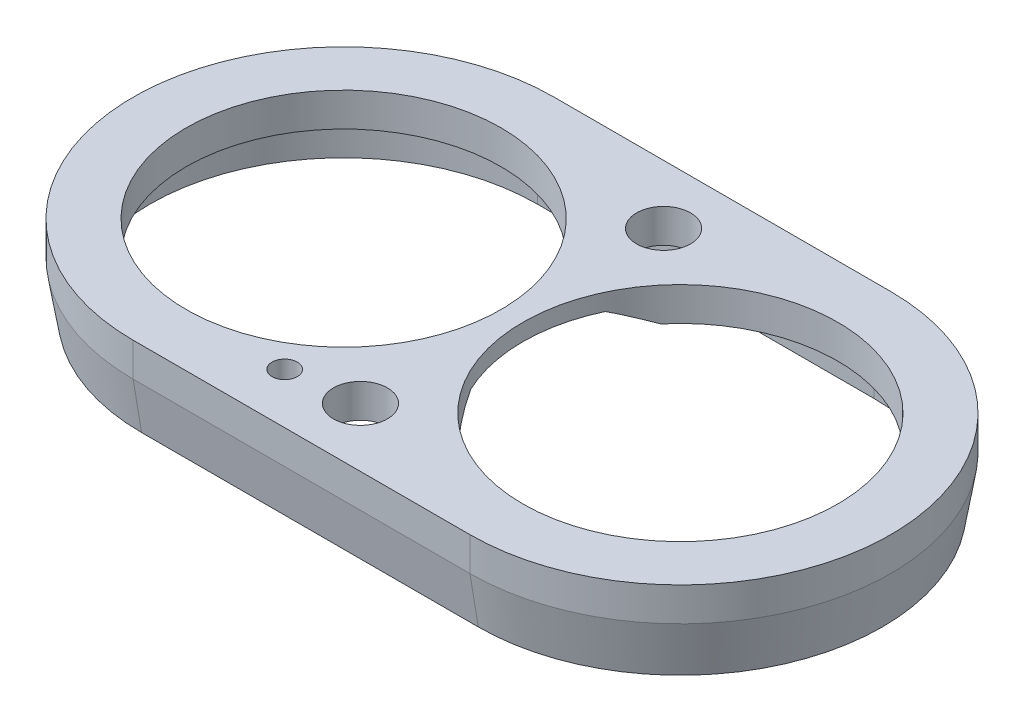
SolidWorks part; units mm, degrees
ref_plane "Front Plane" through (0, 0, 0) normal (0, 0, 1) x (1, 0, 0)
ref_plane "Top Plane" through (0, 0, 0) normal (0, 1, 0) x (1, 0, 0)
ref_plane "Right Plane" through (0, 0, 0) normal (1, 0, 0) x (0, 0, -1)
sketch "Sketch1" plane through (0, 0, 0) normal (0, 1, 0) x (1, 0, 0)
  line L2 (10, -12.5) -> (-10, -12.5)
  line L3 (0, -12.5) -> (0, 12.5)
  line L4 (-0.65, 0) -> (0.65, 0)
  line L6 (31.3696, 0) -> (-34.9839, 0) construction
  line L7 (0, -23.2241) -> (0, 19.3171) construction
  line L8 (10, 12.5) -> (-10, 12.5)
  arc A1 (10, 12.5) -> (10, -12.5) centre (10, 0) cw
  arc A2 (-10, 12.5) -> (-10, -12.5) centre (-10, 0) ccw
  point P22 (0, 0)
  dimension "D2" = 12.5
  dimension "D1" = 10
extrude "Boss-Extrude1" add sketch "Sketch1" along normal blind 2 contours A1 L8 L3 L2 | L8 A2 L2 L3 region at (10.1051, 0, 0) region at (-10.1051, 0, 0)
sketch "Sketch2" plane through (0, 2, 0) normal (0, 1, 0) x (1, 0, 0)
  line L1 (0, 16.1172) -> (0, -16.1351) construction
  circle A0 centre (10, 0) radius 9.35
  circle A1 centre (-10, 0) radius 9.35
  dimension "D2" = 18.7
  dimension "D1" = 10
extrude "Cut-Extrude1" cut sketch "Sketch2" against normal through all
sketch "Sketch3" plane through (0, 0, 0) normal (0, -1, 0) x (1, 0, 0)
  line L4 (-10, -11.5) -> (10, -11.5)
  line L5 (10, 11.5) -> (-10, 11.5)
  line L6 (-10, -11.5) -> (10, -11.5)
  line L7 (10, 11.5) -> (-10, 11.5)
  line L10 (-10, -12.5) -> (10, -12.5)
  line L11 (10, 12.5) -> (-10, 12.5)
  line L12 (-10, -12.5) -> (10, -12.5)
  line L13 (10, 12.5) -> (-10, 12.5)
  arc A4 (10, -11.5) -> (10, 11.5) centre (10, 0) ccw
  arc A5 (-10, 11.5) -> (-10, -11.5) centre (-10, 0) ccw
  arc A6 (10, -11.5) -> (10, 11.5) centre (10, 0) ccw
  arc A7 (-10, 11.5) -> (-10, -11.5) centre (-10, 0) ccw
  arc A10 (10, -12.5) -> (10, 12.5) centre (10, 0) ccw
  arc A11 (-10, 12.5) -> (-10, -12.5) centre (-10, 0) ccw
  arc A12 (10, -12.5) -> (10, 12.5) centre (10, 0) ccw
  arc A13 (-10, 12.5) -> (-10, -12.5) centre (-10, 0) ccw
  dimension "D1" = 1
  dimension "D2" = 0
extrude "Boss-Extrude3" add sketch "Sketch3" along normal blind 3
chamfer "Chamfer1" distance 3 distance2 0.5 4 edges at (22.5, -3, 0) (0, -3, -12.5) (0, -3, 12.5) (-22.5, -3, 0) first distance on face at (16.25, -0.5, 0) first distance on face at (0, -0.5, -12.5) first distance on face at (0, -0.5, 12.5) first distance on face at (-16.25, -0.5, 0)
sketch "Sketch5" plane through (0, 0, 0) normal (0, -1, 0) x (1, 0, 0)
  line L1 (-7.5, -6) -> (7.5, -6)
  line L2 (-7.5, -6) -> (-7.5, 6)
  line L3 (-7.5, 6) -> (7.5, 6)
  line L4 (7.5, -6) -> (7.5, 6)
  line L5 (-7.5, -6) -> (7.5, 6) construction
  line L6 (-7.5, 6) -> (7.5, -6) construction
  point P0 (0, 0)
  dimension "D1" = 15
  dimension "D2" = 12
extrude "Cut-Extrude3" cut sketch "Sketch5" against normal blind 1
chamfer "Chamfer2" distance 1 distance2 2 2 edges at (0, 1, -6) (0, 1, 6) first distance on face at (0, 0.5, -6) first distance on face at (0, 0.5, 6)
sketch "Sketch7" plane through (0, 2, 0) normal (0, 1, 0) x (1, 0, 0)
  line L0 (10, -12.5) -> (-10, -12.5) construction
  line L1 (10, 12.5) -> (-10, 12.5) construction
  circle A0 centre (-4, -9.5) radius 0.75
  circle A1 centre (0, -9) radius 1.6
  circle A2 centre (0, 9) radius 1.6
  dimension "D1" = 1.5
  dimension "D4" = 3.2
  dimension "D7" = 3.2
  dimension "D2" = 3
  dimension "D3" = 4
  dimension "D5" = 3.5
  dimension "D6" = 3.5
extrude "Cut-Extrude4" cut sketch "Sketch7" against normal through all
